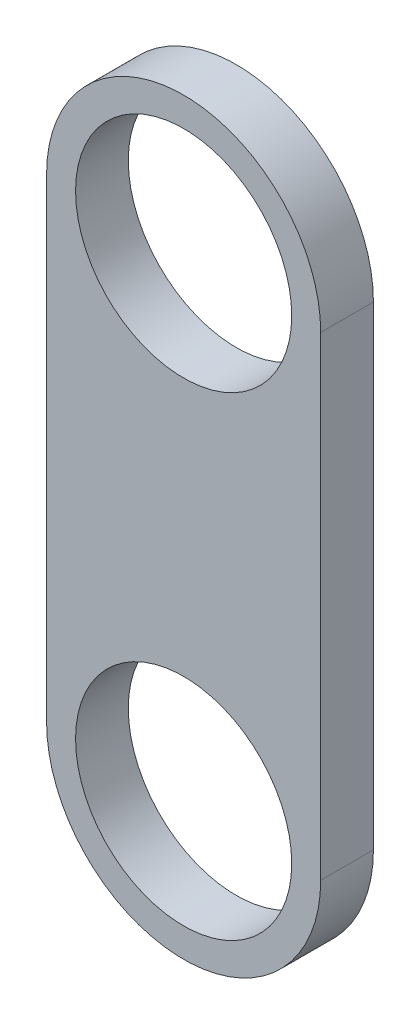
SolidWorks part; units mm, degrees
ref_plane "Front Plane" through (0, 0, 0) normal (0, 0, 1) x (1, 0, 0)
ref_plane "Top Plane" through (0, 0, 0) normal (0, 1, 0) x (1, 0, 0)
ref_plane "Right Plane" through (0, 0, 0) normal (1, 0, 0) x (0, 0, -1)
sketch "Sketch1" plane through (0, 0, 0) normal (0, 0, 1) x (1, 0, 0)
  line L0 (0, 0) -> (0, -45) construction
  line L1 (10.25, 0) -> (10.25, -45)
  line L2 (-10.25, 0) -> (-10.25, -45)
  line L3 (0, 0) -> (0, -45) construction
  line L4 (13, 0) -> (13, -45)
  line L5 (-13, 0) -> (-13, -45)
  arc A0 (10.25, 0) -> (-10.25, 0) centre (0, 0) ccw
  arc A1 (-10.25, -45) -> (10.25, -45) centre (0, -45) ccw
  circle A2 centre (0, 0) radius 10.25
  circle A3 centre (0, -45) radius 10.25
  arc A4 (13, 0) -> (-13, 0) centre (0, 0) ccw
  arc A5 (-13, -45) -> (13, -45) centre (0, -45) ccw
  circle A6 centre (0, 0) radius 8
  circle A7 centre (0, 8) radius 1.2
  circle A8 centre (8, 0) radius 1.2
  circle A9 centre (0, -8) radius 1.2
  circle A10 centre (-8, 0) radius 1.2
  point P3 (0, -22.5)
  point P12 (0, -22.5)
  point P30 (0, 0)
  dimension "D1" = 10.25
  dimension "D3" = 13
  dimension "D4" = 16
  dimension "D5" = 2.4
  dimension "D2" = 45
  dimension "D6" = 4
extrude "Boss-Extrude1" add sketch "Sketch1" along normal blind 5 contours L5 A5 L4 A4 A1 L2 A0 L1 | A3 L1 A2 L2 region at (0, -22.5, 0) region at (12.2439, -22.5, 0)
